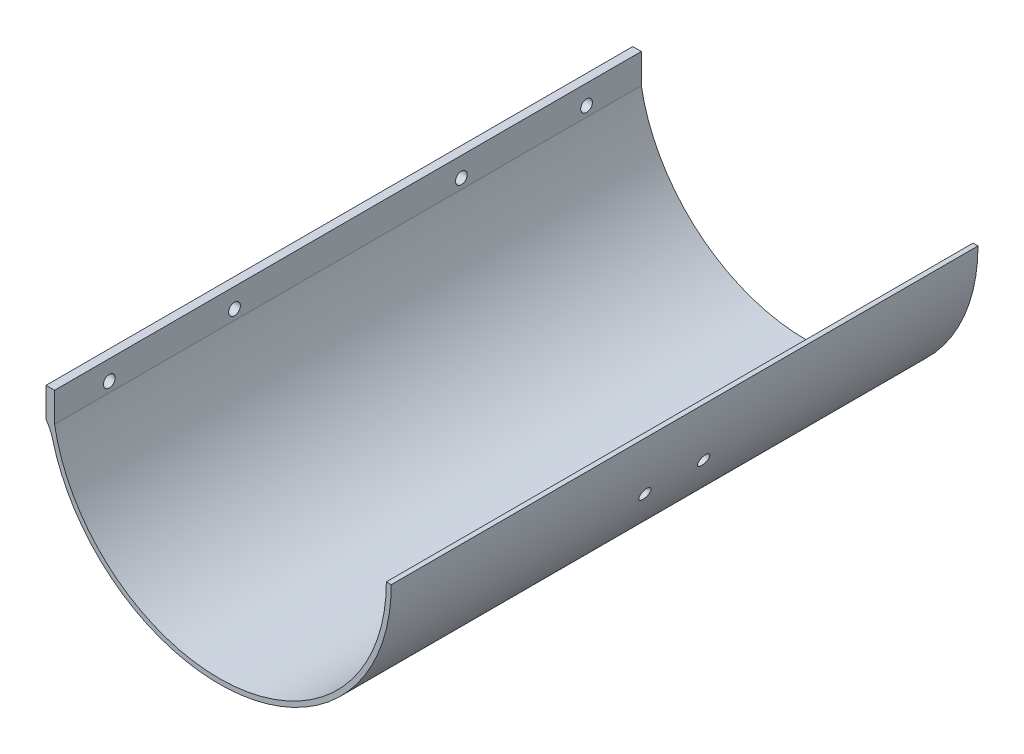
SolidWorks part; units mm, degrees
ref_plane "Front Plane" through (0, 0, 0) normal (0, 0, 1) x (1, 0, 0)
ref_plane "Top Plane" through (0, 0, 0) normal (0, 1, 0) x (1, 0, 0)
ref_plane "Right Plane" through (0, 0, 0) normal (1, 0, 0) x (0, 0, -1)
sketch "Sketch1" plane through (0, 0, 0) normal (0, 0, 1) x (1, 0, 0)
  line L0 (-44, 0) -> (-42.75, 0)
  line L1 (42.75, 0) -> (44, 0)
  arc A0 (-44, 0) -> (44, 0) centre (0, 0) ccw
  arc A1 (-42.75, 0) -> (42.75, 0) centre (0, 0) ccw
  dimension "D1" = 88
  dimension "D2" = 85.5
extrude "Boss-Extrude1" add sketch "Sketch1" along normal blind 150
sketch "Sketch2" plane through (0, 0, 0) normal (1, 0, 0) x (0, 0, -1)
  line L2 (-150, 0) -> (0, 0) construction
  line L3 (-150, 0) -> (-150, -44) construction
  circle A0 centre (-136, -5) radius 1.5
  circle A1 centre (-104, -5) radius 1.5
  circle A2 centre (-46, -5) radius 1.5
  circle A3 centre (-14, -5) radius 1.5
  dimension "D1" = 3
  dimension "D2" = 3
  dimension "D3" = 3
  dimension "D4" = 3
  dimension "D5" = 32
  dimension "D6" = 32
  dimension "D7" = 58
  dimension "D8" = 14
  dimension "D10" = 5
extrude "Cut-Extrude1" cut sketch "Sketch2" against normal up to surface (43.715 mm away) up to face at (0, -22, 75)
ref_plane "Plane1" through (0, 0, 72) normal (0, 0, -1) x (-1, 0, 0)
sketch "Sketch4" plane through (0, 0, 72) normal (0, 0, -1) x (-1, 0, 0)
  line L0 (-42.1884, 12.4954) -> (-40.8831, 12.4954)
  line L1 (-44, 0) -> (-42.75, 0)
  arc A0 (-40.8831, 12.4954) -> (-42.75, 0) centre (0, 0) ccw
  arc A1 (-42.1884, 12.4954) -> (-44, 0) centre (0, 0) ccw
  dimension "D1" = 88
  dimension "D2" = 85.5
extrude "Boss-Extrude2" add sketch "Sketch4" along normal blind 7.5 and the other way blind 7.5
sketch "Sketch5" plane through (0, 0, 150) normal (0, 0, 1) x (1, 0, 0)
  line L5 (-44, 0) -> (-44, -7.5543)
  line L6 (-44, -7.5543) -> (-42.7628, -7.5543)
  line L7 (-42.7628, -7.5543) -> (-42.7628, 0)
  line L8 (-42.75, 0) -> (-44, 0) construction
  line L9 (-42.7628, 0) -> (-44, 0)
extrude "Cut-Extrude2" cut sketch "Sketch5" against normal up to surface (150 mm away) up to face at (0, -21.6875, 0)
sketch "Sketch6" plane through (-42.7628, 0, 0) normal (-1, 0, 0) x (0, 0, 1)
  line L1 (0, -7.5543) -> (150, -7.5543)
  line L2 (0, -7.5543) -> (0, 0)
  line L3 (0, 0) -> (150, 0)
  line L4 (150, -7.5543) -> (150, 0)
  circle A0 centre (14, -5) radius 1.5
  circle A1 centre (46, -5) radius 1.5
  circle A2 centre (104, -5) radius 1.5
  circle A3 centre (136, -5) radius 1.5
  circle M5 centre (46, -5) radius 1.5
  circle M6 centre (136, -5) radius 1.5
  line M7 (0, 0) -> (0, -7.5543)
  line M8 (0, -7.5543) -> (150, -7.5543)
  line M9 (150, -7.5543) -> (150, 0)
  line M10 (150, 0) -> (0, 0)
  circle M11 centre (104, -5) radius 1.5
  circle M12 centre (14, -5) radius 1.5
extrude "Boss-Extrude3" add sketch "Sketch6" along normal blind 0.5 contours M10 M7 M8 M9 M6 M11 M12 M5 region at (-42.7628, -3.7459, 75)
sketch "Sketch7" plane through (0, 0, 150) normal (0, 0, 1) x (1, 0, 0)
  line L0 (3.1936, -47.2716) -> (4.2473, -46.1824)
  line L2 (2.6526, -44.3202) -> (7.0646, -42.9225)
  line L3 (2.6526, -44.3202) -> (-0.0812, -45.0066)
  line L4 (-2.6526, -44.3202) -> (-7.0646, -42.9225)
  arc A1 (-0.0812, -45.0066) -> (3.1936, -47.2716) centre (-0.0812, -48.5066) ccw
  arc A2 (-2.6526, -44.3202) -> (4.2473, -46.1824) centre (-0.0812, -48.5066) ccw
  arc A3 (-7.0646, -42.9225) -> (7.0646, -42.9225) centre (0, 0) ccw
  dimension "D1" = 43.5
  dimension "D2" = 7
extrude "Boss-Extrude4" add sketch "Sketch7" against normal blind 80
fillet "Fillet3" radius 0.5 1 edges at (4.2473, -46.1824, 110)
sketch "Sketch9" plane through (0, 0, 0) normal (1, 0, 0) x (0, 0, -1)
  line L0 (-79.5, 12.4954) -> (-79.5, 0) construction
  line L1 (-78, 8.4954) -> (-66, 8.4954)
  line L2 (-78, 8.4954) -> (-78, 2.4954)
  line L3 (-78, 2.4954) -> (-66, 2.4954)
  line L4 (-66, 8.4954) -> (-66, 2.4954)
  line L5 (-79.5, 12.4954) -> (-64.5, 12.4954) construction
  dimension "D1" = 12
  dimension "D2" = 6
  dimension "D3" = 1.5
  dimension "D4" = 4
extrude "Cut-Extrude4" cut sketch "Sketch9" along normal up to surface (43.1721 mm away) up to face at (15.0324, -18.3013, 85.6667)
sketch "Sketch11" plane through (0, 0, 150) normal (0, 0, 1) x (1, 0, 0)
  line L1 (6.0382, -53.7585) -> (4.3409, -43.7853)
  line L2 (6.0382, -53.7585) -> (2.0015, -51.3196)
  line L3 (-6.6638, -46.7537) -> (-4.3409, -43.7853)
  line L4 (2.6526, -44.3202) -> (4.3409, -43.7853) construction
  arc A1 (-6.6638, -46.7537) -> (6.0382, -53.7585) centre (2.0015, -46.0596) ccw
  arc A2 (-4.3409, -43.7853) -> (4.3409, -43.7853) centre (0, 0) ccw
  arc A3 (-0.0812, -45.0066) -> (3.1936, -47.2716) centre (-0.0812, -48.5066) ccw construction
  arc A4 (4.3409, -43.7853) -> (44, 0) centre (0, 0) ccw construction
  dimension "D1" = 44
extrude "Cut-Extrude5" cut sketch "Sketch11" against normal blind 67 contours A1 L3 A2 L1
sketch "Sketch12" plane through (0, 0, 0) normal (0, 0, -1) x (-1, 0, 0)
  line L2 (42.75, 0) -> (42.75, -7.5543)
  line L6 (42.75, -7.5543) -> (41.523, -7.5543)
  line L7 (41.523, -7.5543) -> (42.75, 0)
extrude "Cut-Extrude6" cut sketch "Sketch12" against normal up to surface (150 mm away) up to face at (-13.7346, -16.3196, 150)
sketch "Sketch14" plane through (-43.2628, 0, 0) normal (-1, 0, 0) x (0, 0, 1)
  line L0 (0, -7.5543) -> (150, -7.5543) construction
  line L1 (0, 0) -> (150, 0)
  line L2 (0, 0) -> (0, -7.5543)
  line L3 (0, -7.5543) -> (150, -7.5543)
  line L4 (150, 0) -> (150, -7.5543)
  line L5 (150, -7.5543) -> (150, 0) construction
  circle A0 centre (14, -5) radius 1.5
  circle A1 centre (46, -5) radius 1.5
  circle A2 centre (104, -5) radius 1.5
  circle A3 centre (136, -5) radius 1.5
extrude "Boss-Extrude5" add sketch "Sketch14" along normal blind 1 and the other way blind 1.5
sketch "Sketch17" plane through (0, -7.5543, 0) normal (0, -1, 0) x (1, 0, 0)
  line L1 (-42.0773, 150) -> (-41.7628, 150)
  line L2 (-42.0773, 150) -> (-42.0773, 0)
  line L3 (-42.0773, 0) -> (-41.7628, 0)
  line L4 (-41.7628, 150) -> (-41.7628, 0)
extrude "Cut-Extrude8" cut sketch "Sketch17" against normal up to surface (7.5543 mm away) up to face at (-43.0128, 0, 75)
fillet "Fillet4" radius 10 1 edges at (-43.3467, -7.5543, 75)
sketch "Sketch18" plane through (0, 0, 79.5) normal (0, 0, 1) x (1, 0, 0)
  line L1 (40.1344, 0) -> (45.8139, 0)
  line L2 (40.1344, 0) -> (40.1344, 15.0548)
  line L3 (40.1344, 15.0548) -> (45.8139, 15.0548)
  line L4 (45.8139, 0) -> (45.8139, 15.0548)
extrude "Cut-Extrude9" cut sketch "Sketch18" against normal up to surface (15 mm away) up to face at (42.6841, 6.2814, 64.5)
sketch "Sketch19" plane through (-42.0773, 0, 0) normal (1, 0, 0) x (0, 0, -1)
  line L0 (-75, 0) -> (-75, -20.7313) construction
  line L1 (-150, 0) -> (0, 0) construction
  circle A0 centre (-82.5, -15) radius 1.5
  circle A1 centre (-67.5, -15) radius 1.5
  dimension "D1" = 3
  dimension "D2" = 3
  dimension "D3" = 15
  dimension "D4" = 7.5
  dimension "D5" = 15
extrude "Cut-Extrude10" cut sketch "Sketch19" along normal up to surface (63.4415 mm away) from offset 20 up to face at (3.1311, -24.5812, 75)
